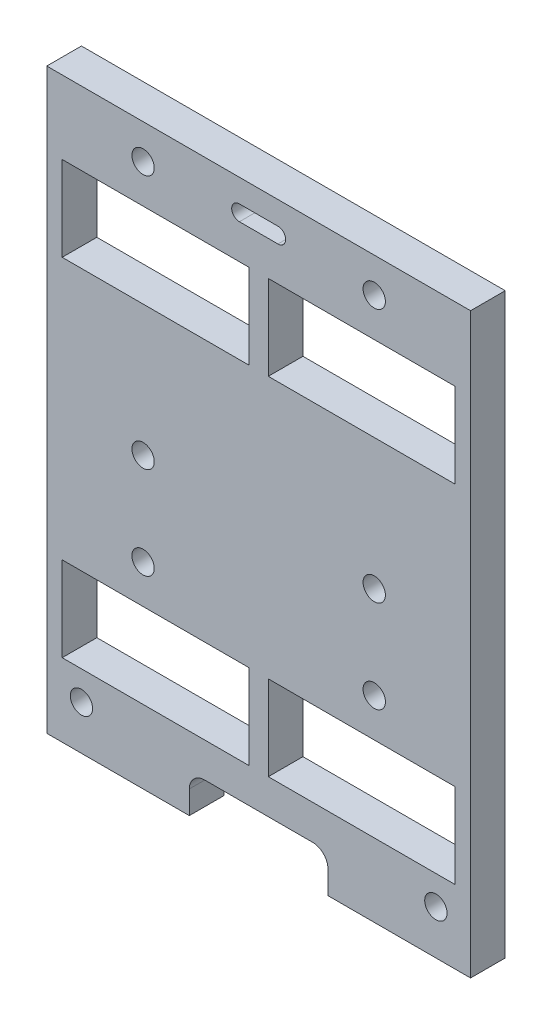
SolidWorks part; units mm, degrees
ref_plane "Front Plane" through (0, 0, 0) normal (0, 0, 1) x (1, 0, 0)
ref_plane "Top Plane" through (0, 0, 0) normal (0, 1, 0) x (1, 0, 0)
ref_plane "Right Plane" through (0, 0, 0) normal (1, 0, 0) x (0, 0, -1)
sketch "Sketch1" plane through (0, 0, 0) normal (0, 0, 1) x (1, 0, 0)
  line L0 (0, -37.5) -> (0, 37.5) construction
  line L1 (-27.5, -37.5) -> (27.5, -37.5)
  line L2 (-27.5, -37.5) -> (-27.5, 37.5)
  line L3 (-27.5, 37.5) -> (27.5, 37.5)
  line L4 (27.5, -37.5) -> (27.5, 37.5)
  line L5 (-27.5, -37.5) -> (27.5, 37.5) construction
  line L6 (-27.5, 37.5) -> (27.5, -37.5) construction
  line L7 (-27.5, 0) -> (27.5, 0) construction
  line L8 (-27.5, 22.5) -> (27.5, 22.5) construction
  line L9 (25.5, 17) -> (1.25, 28) construction
  line L10 (-25.5, 28) -> (-1.25, 28)
  line L11 (-25.5, 28) -> (-25.5, 17)
  line L12 (-25.5, 17) -> (-1.25, 17)
  line L13 (-1.25, 28) -> (-1.25, 17)
  line L14 (-25.5, 28) -> (-1.25, 17) construction
  line L15 (-25.5, 17) -> (-1.25, 28) construction
  line L16 (25.5, 28) -> (1.25, 17) construction
  line L17 (1.25, 28) -> (1.25, 17)
  line L18 (25.5, 17) -> (1.25, 17)
  line L19 (25.5, 28) -> (25.5, 17)
  line L20 (25.5, 28) -> (1.25, 28)
  line L21 (25.5, -28) -> (1.25, -17) construction
  line L22 (-25.5, -17) -> (-1.25, -28) construction
  line L23 (-25.5, -28) -> (-1.25, -17) construction
  line L24 (25.5, -17) -> (1.25, -28) construction
  line L25 (25.5, -28) -> (1.25, -28)
  line L26 (25.5, -28) -> (25.5, -17)
  line L27 (25.5, -17) -> (1.25, -17)
  line L28 (1.25, -28) -> (1.25, -17)
  line L29 (-1.25, -28) -> (-1.25, -17)
  line L30 (-25.5, -17) -> (-1.25, -17)
  line L31 (-25.5, -28) -> (-25.5, -17)
  line L32 (-25.5, -28) -> (-1.25, -28)
  point P0 (0, 0)
  point P12 (-13.375, 22.5)
  point P21 (13.375, 22.5)
  point P30 (13.375, -22.5)
  point P31 (-13.375, -22.5)
  dimension "D1" = 55
  dimension "D2" = 75
  dimension "D3" = 22.5
  dimension "D4" = 24.25
  dimension "D5" = 11
  dimension "D6" = 1.25
extrude "Boss-Extrude1" add sketch "Sketch1" along normal blind 4.5
sketch "Sketch2" plane through (0, 0, 4.5) normal (0, 0, 1) x (1, 0, 0)
  line L0 (0, -37.5) -> (0, 37.5) construction
  line L1 (-27.5, -37.5) -> (27.5, -37.5) construction
  line L2 (27.5, 37.5) -> (-27.5, 37.5) construction
  line L3 (-27.5, 0) -> (27.5, 0) construction
  line L4 (-27.5, 37.5) -> (-27.5, -37.5) construction
  line L5 (27.5, -37.5) -> (27.5, 37.5) construction
  line L6 (-15, 0) -> (15, 0) construction
  circle A0 centre (-15, 33) radius 1.45
  circle A1 centre (15, 33) radius 1.45
  circle A2 centre (15, 0) radius 1.45
  circle A3 centre (-15, 0) radius 1.45
  dimension "D1" = 2.9
  dimension "D7" = 2.9
  dimension "D8" = 2.9
  dimension "D2" = 15
  dimension "D3" = 33
  dimension "D4" = 30
  dimension "D5" = 15
  dimension "D6" = 0
extrude "screwHoles" cut sketch "Sketch2" against normal through all
sketch "Sketch3" plane through (0, 0, 4.5) normal (0, 0, 1) x (1, 0, 0)
  line L0 (-27.5, 9) -> (26.0486, 9) construction
  line L1 (-27.5, 37.5) -> (-27.5, -37.5) construction
  line L3 (0, 37.5) -> (0, -37.5) construction
  line L4 (27.5, 37.5) -> (-27.5, 37.5) construction
  line L5 (-27.5, -37.5) -> (27.5, -37.5) construction
  line L6 (18.95, 6.8) -> (9.05, 11.2) construction
  line L7 (-18.95, 11.2) -> (-9.05, 11.2)
  line L8 (-18.95, 11.2) -> (-18.95, 6.8)
  line L9 (-18.95, 6.8) -> (-9.05, 6.8)
  line L10 (-9.05, 11.2) -> (-9.05, 6.8)
  line L11 (-18.95, 11.2) -> (-9.05, 6.8) construction
  line L12 (-18.95, 6.8) -> (-9.05, 11.2) construction
  line L13 (18.95, 11.2) -> (9.05, 6.8) construction
  line L14 (9.05, 11.2) -> (9.05, 6.8)
  line L15 (18.95, 6.8) -> (9.05, 6.8)
  line L16 (18.95, 11.2) -> (18.95, 6.8)
  line L17 (18.95, 11.2) -> (9.05, 11.2)
  line L18 (-27.5, 37.5) -> (-27.5, -37.5) construction
  point P2 (-27.5, 0)
  point P12 (-14, 9)
  point P21 (14, 9)
  dimension "D1" = 9.9
  dimension "D2" = 4.4
  dimension "D3" = 14
  dimension "D4" = 9
extrude "BeltClamp" [suppressed] cut sketch "Sketch3" against normal through all
sketch "Sketch4" plane through (0, 0, 4.5) normal (0, 0, 1) x (1, 0, 0)
  line L0 (-27.5, 0) -> (27.5, 0) construction
  line L1 (-27.5, 37.5) -> (-27.5, -37.5) construction
  line L2 (27.5, -37.5) -> (27.5, 37.5) construction
  line L4 (-4.8, 2.15) -> (4.8, 2.15)
  line L5 (-4.8, 2.15) -> (-4.8, -2.15)
  line L6 (-4.8, -2.15) -> (4.8, -2.15)
  line L7 (4.8, 2.15) -> (4.8, -2.15)
  line L8 (-4.8, 2.15) -> (4.8, -2.15) construction
  line L9 (-4.8, -2.15) -> (4.8, 2.15) construction
  circle A0 centre (-15, 0) radius 1.45 construction
  point P6 (0, 0)
  dimension "D1" = 9.6
  dimension "D2" = 4.3
  dimension "D3" = 0
extrude "mountingPlateTab" [suppressed] cut sketch "Sketch4" against normal through all
sketch "Sketch5" plane through (0, 0, 4.5) normal (0, 0, 1) x (1, 0, 0)
  line L0 (-27.5, -9.75) -> (27.5, -9.75) construction
  line L1 (-27.5, 37.5) -> (-27.5, -37.5) construction
  line L2 (27.5, -37.5) -> (27.5, 37.5) construction
  line L4 (0, -37.5) -> (0, 37.5) construction
  line L5 (-27.5, -37.5) -> (27.5, -37.5) construction
  line L6 (27.5, 37.5) -> (-27.5, 37.5) construction
  line L7 (-20.85, -14.55) -> (-25.15, -4.95) construction
  line L8 (20.85, -4.95) -> (25.15, -4.95)
  line L9 (20.85, -4.95) -> (20.85, -14.55)
  line L10 (20.85, -14.55) -> (25.15, -14.55)
  line L11 (25.15, -4.95) -> (25.15, -14.55)
  line L12 (20.85, -4.95) -> (25.15, -14.55) construction
  line L13 (20.85, -14.55) -> (25.15, -4.95) construction
  line L14 (-20.85, -4.95) -> (-25.15, -14.55) construction
  line L15 (-25.15, -4.95) -> (-25.15, -14.55)
  line L16 (-20.85, -14.55) -> (-25.15, -14.55)
  line L17 (-20.85, -4.95) -> (-20.85, -14.55)
  line L18 (-20.85, -4.95) -> (-25.15, -4.95)
  line L19 (23, -9.75) -> (23, -37.5) construction
  line L20 (-23, -9.75) -> (-23, -37.5) construction
  circle A0 centre (23, -31.75) radius 1.45
  circle A1 centre (-23, -31.75) radius 1.45
  point P15 (23, -9.75)
  point P24 (-23, -9.75)
  dimension "D5" = 2.9
  dimension "D2" = 9.6
  dimension "D3" = 4.3
  dimension "D4" = 23
  dimension "D6" = 22
  dimension "D1" = 9.75
extrude "BraceTabs" cut sketch "Sketch5" against normal through all
sketch "Sketch6" [suppressed] plane through (0, 0, 4.5) normal (0, 0, 1) x (1, 0, 0)
  line L0 (-25.2, -9.75) -> (25.2, -9.75) construction
  line L1 (-25.2, -4.85) -> (-25.2, -14.65) construction
  line L2 (25.2, -14.65) -> (25.2, -4.85) construction
  line L3 (0, -2.2) -> (0, -37.5) construction
  line L4 (-4.9, -2.2) -> (4.9, -2.2) construction
  line L5 (-27.5, -37.5) -> (27.5, -37.5) construction
  line L6 (23, -14.65) -> (23, -4.85) construction
  line L7 (20.8, -14.65) -> (25.2, -14.65) construction
  line L8 (25.2, -4.85) -> (20.8, -4.85) construction
  line L9 (20.8, -4.85) -> (20.8, -14.65) construction
  line L10 (19.8, -15.65) -> (26.2, -15.65)
  line L11 (19.8, -15.65) -> (19.8, -3.85)
  line L12 (19.8, -3.85) -> (26.2, -3.85)
  line L13 (26.2, -15.65) -> (26.2, -3.85)
  line L14 (19.8, -15.65) -> (26.2, -3.85) construction
  line L15 (19.8, -3.85) -> (26.2, -15.65) construction
  line L16 (-19.8, -3.85) -> (-26.2, -15.65) construction
  line L17 (-19.8, -15.65) -> (-26.2, -3.85) construction
  line L18 (-23, -14.65) -> (-23, -4.85) construction
  line L19 (-26.2, -15.65) -> (-26.2, -3.85)
  line L20 (-19.8, -3.85) -> (-26.2, -3.85)
  line L21 (-19.8, -15.65) -> (-19.8, -3.85)
  line L22 (-19.8, -15.65) -> (-26.2, -15.65)
  circle A0 centre (23, -9.75) radius 1.45
  circle A1 centre (-23, -9.75) radius 1.45
  point P18 (23, -9.75)
  dimension "D3" = 2.9
  dimension "D1" = 1
  dimension "D2" = 1
extrude "FrontToRear1" [suppressed] add sketch "Sketch6" against normal up to surface (4.5 mm away) up to face at (-24.45, -31.75, 0)
sketch "Sketch7" [suppressed] plane through (0, 0, 4.5) normal (0, 0, 1) x (1, 0, 0)
  line L0 (4.9, 2.2) -> (-4.9, 2.2) construction
  line L1 (-20, -3.2) -> (20, -3.2)
  line L2 (-20, -3.2) -> (-20, 3.2)
  line L3 (-20, 3.2) -> (20, 3.2)
  line L4 (20, -3.2) -> (20, 3.2)
  line L5 (-20, -3.2) -> (20, 3.2) construction
  line L6 (-20, 3.2) -> (20, -3.2) construction
  circle A0 centre (15, 0) radius 1.45 construction
  point P0 (0, 0)
  dimension "D1" = 1
  dimension "D2" = 5
extrude "FrontToRear2" [suppressed] add sketch "Sketch7" against normal through all
sketch "Sketch8" plane through (0, 0, 4.5) normal (0, 0, 1) x (1, 0, 0)
  line L0 (-27.5, -12) -> (27.5, -12) construction
  line L1 (-27.5, 37.5) -> (-27.5, -37.5) construction
  line L2 (27.5, -37.5) -> (27.5, 37.5) construction
  line L3 (0, -37.5) -> (0, 0) construction
  line L4 (-27.5, -37.5) -> (27.5, -37.5) construction
  circle A0 centre (-15, -12) radius 1.45
  circle A1 centre (15, -12) radius 1.45
  dimension "D2" = 2.9
  dimension "D1" = 12
  dimension "D3" = 15
extrude "ExpansionScrewholes" cut sketch "Sketch8" against normal through all
sketch "Sketch12" plane through (0, 0, 4.5) normal (0, 0, 1) x (1, 0, 0)
  line L0 (0, 37.5) -> (0, 0) construction
  line L1 (27.5, 37.5) -> (-27.5, 37.5) construction
  line L2 (-2.5, 33.5) -> (2.5, 33.5) construction
  line L3 (-2.5, 34.5) -> (2.5, 34.5)
  line L4 (-2.5, 32.5) -> (2.5, 32.5)
  arc A0 (-2.5, 34.5) -> (-2.5, 32.5) centre (-2.5, 33.5) ccw
  arc A1 (2.5, 32.5) -> (2.5, 34.5) centre (2.5, 33.5) ccw
  point P7 (0, 33.5)
  dimension "D1" = 3
  dimension "D2" = 2
  dimension "D3" = 5
extrude "CableTieSlot" cut sketch "Sketch12" against normal through all
sketch "Sketch11" plane through (0, 0, 4.5) normal (0, 0, 1) x (1, 0, 0)
  line L0 (13.5615, -8.55) -> (27.5, -8.55) construction
  line L1 (27.5, -37.5) -> (27.5, 37.5) construction
  line L2 (0, 37.5) -> (0, -37.5) construction
  line L3 (36.5, -14.55) -> (18.5, -14.55)
  line L4 (36.5, -14.55) -> (36.5, -2.55)
  line L5 (36.5, -2.55) -> (18.5, -2.55)
  line L6 (18.5, -14.55) -> (18.5, -2.55)
  line L7 (36.5, -14.55) -> (18.5, -2.55) construction
  line L8 (36.5, -2.55) -> (18.5, -14.55) construction
  line L11 (-36.5, -2.55) -> (-18.5, -14.55) construction
  line L12 (-36.5, -14.55) -> (-18.5, -2.55) construction
  line L13 (-18.5, -14.55) -> (-18.5, -2.55)
  line L14 (-36.5, -2.55) -> (-18.5, -2.55)
  line L15 (-36.5, -14.55) -> (-36.5, -2.55)
  line L16 (-36.5, -14.55) -> (-18.5, -14.55)
  line L17 (36.5, -2.55) -> (18.5, -14.55) construction
  line L18 (20.85, -14.55) -> (25.15, -14.55) construction
  line L19 (27.5, 37.5) -> (-27.5, 37.5) construction
  line L20 (-27.5, -37.5) -> (27.5, -37.5) construction
  dimension "D1" = 9
  dimension "D2" = 12
  dimension "D3" = 0
extrude "Cut-Extrude2" [suppressed] cut sketch "Sketch11" against normal through all
sketch "Sketch10" [suppressed] plane through (0, 0, 4.5) normal (0, 0, 1) x (1, 0, 0)
  line L0 (4.7446, 1) -> (27.5, 1) construction
  line L1 (-4.9, 0) -> (4.9, 0) construction
  line L2 (27.5, -37.5) -> (27.5, 37.5) construction
  line L3 (0, 2.2) -> (0, -2.2) construction
  line L4 (36.5, 4) -> (18.5, 4)
  line L5 (36.5, 4) -> (36.5, -2)
  line L6 (36.5, -2) -> (18.5, -2)
  line L7 (18.5, 4) -> (18.5, -2)
  line L8 (36.5, 4) -> (18.5, -2) construction
  line L9 (36.5, -2) -> (18.5, 4) construction
  line L10 (4.9, 2.2) -> (-4.9, 2.2) construction
  line L11 (-4.9, -2.2) -> (4.9, -2.2) construction
  line L12 (-36.5, -2) -> (-18.5, 4) construction
  line L13 (-36.5, 4) -> (-18.5, -2) construction
  line L14 (-4.7446, 1) -> (-27.5, 1) construction
  line L15 (-18.5, 4) -> (-18.5, -2)
  line L16 (-36.5, -2) -> (-18.5, -2)
  line L17 (-36.5, 4) -> (-36.5, -2)
  line L18 (-36.5, 4) -> (-18.5, 4)
  line L19 (36.5, -2) -> (18.5, 4) construction
  line L20 (-4.9, 2.2) -> (-4.9, -2.2) construction
  line L21 (4.9, -2.2) -> (4.9, 2.2) construction
  dimension "D1" = 6
  dimension "D2" = 9
  dimension "D3" = 1
extrude "CableTieSlots" [suppressed] cut sketch "Sketch10" against normal through all
sketch "Sketch9" plane through (0, 0, 4.5) normal (0, 0, 1) x (1, 0, 0)
  line L0 (-27.5, -37.5) -> (27.5, -37.5) construction
  line L5 (-9, -42.5) -> (9, -42.5)
  line L6 (-9, -42.5) -> (-9, -34.5)
  line L7 (-7, -32.5) -> (7, -32.5)
  line L8 (9, -42.5) -> (9, -34.5)
  line L9 (-9, -42.5) -> (9, -32.5) construction
  line L10 (-9, -32.5) -> (9, -42.5) construction
  arc A0 (7, -32.5) -> (9, -34.5) centre (7, -34.5) cw
  arc A1 (-9, -34.5) -> (-7, -32.5) centre (-7, -34.5) cw
  point P9 (0, -37.5)
  line M42 (-27.5, -37.5) -> (27.5, -37.5)
  dimension "D3" = 2
  dimension "D1" = 18
  dimension "D2" = 5
extrude "RearFanSlot" cut sketch "Sketch9" against normal through all contours A1 L6 L8 A0 L7 M42 | L5 L8 L6 M42
sketch "Sketch13" [suppressed] plane through (0, 0, 4.5) normal (0, 0, 1) x (1, 0, 0)
  line L1 (-7, -2.85) -> (7, -2.85)
  line L2 (-7, -2.85) -> (-7, -11.85)
  line L3 (-7, -11.85) -> (7, -11.85)
  line L4 (7, -2.85) -> (7, -11.85)
  line L5 (-7, -2.85) -> (7, -11.85) construction
  line L6 (-7, -11.85) -> (7, -2.85) construction
  line L9 (0, 37.5) -> (0, -7.35) construction
  line L10 (-18.5, -2.85) -> (-27.5, -2.85) construction
  line L11 (27.5, 37.5) -> (-27.5, 37.5) construction
  line L13 (-27.5, -14.85) -> (-18.5, -14.85) construction
  point P0 (0, -7.35)
  dimension "D1" = 3
  dimension "D2" = 0
  dimension "D3" = 7
extrude "Cut-Extrude3" [suppressed] cut sketch "Sketch13" against normal through all
sketch "Sketch14" plane through (0, 0, 4.5) normal (0, 0, 1) x (1, 0, 0)
  line L0 (25.15, -4.95) -> (20.85, -4.95) construction
  line L1 (25.15, -4.95) -> (20.85, -4.95)
  line L2 (25.15, -4.95) -> (25.15, -14.55)
  line L3 (25.15, -14.55) -> (20.85, -14.55)
  line L4 (20.85, -4.95) -> (20.85, -14.55)
  line L5 (25.15, -14.55) -> (25.15, -4.95) construction
  line L6 (0, 0) -> (0, -6.835) construction
  line L7 (-20.85, -4.95) -> (-20.85, -14.55)
  line L8 (-25.15, -14.55) -> (-20.85, -14.55)
  line L9 (-25.15, -4.95) -> (-25.15, -14.55)
  line L10 (-25.15, -4.95) -> (-20.85, -4.95)
extrude "Boss-Extrude2" add sketch "Sketch14" against normal through all
equation "\"X-ROD-SPACING\"=45"
equation "\"Y-ROD-SPACING\"=75"
equation "\"Z-ROD-SPACING\"=17.5"
equation "\"Y-BED-OFFSET\"=2"
equation "\"Y-BED-ROD-INSET\"=3.5"
equation "\"Y-BED-SCREW-SPACING\"=209"
equation "\"Y-BED-SCREW-CUTOUT-SLOT-HEIGHT\"=2"
equation "\"T-SLOT-NUT-FILLET-RADIUS\"=0.5"
equation "\"T-SLOT-SCREW-SHAFT-RADIUS\"=1.55"
equation "\"T-SLOT-SCREW-SHAFT-CUTOUT-LENGTH\"=11.0"
equation "\"T-SLOT-NUT-DEPTH\"=3.5"
equation "\"T-SLOT-NUT-WIDTH\"=2.85"
equation "\"T-SLOT-NUT-END-DISTANCE\"=8"
equation "\"ACRYLIC-THICKNESS\"=10"
equation "\"ACRYLIC-THICKNESS2\"=4.5"
equation "\"ACRYLIC-TAB-CUTOUT-SIZE\"=\"ACRYLIC-THICKNESS\"+\"ACRYLIC-TAB-TOLERANCE\"*2"
equation "\"ACRYLIC-TAB-WIDTH\"=\"ACRYLIC-THICKNESS\""
equation "\"ACRYLIC-M3-HOLE\"=2.9"
equation "\"SMOOTHROD-CAP-SCREW-DISTANCE\"=20"
equation "\"FRAME-WIDTH-INNER\"=370"
equation "\"NEMA17-HOLE-SPACING\"=31"
equation "\"NEMA17-CENTRAL-CUTOUT\"=22.5"
equation "\"Z-BRACKET-REACH\"=55"
equation "\"Z-ROD-INSET\"=16"
equation "\"TOP-BRACKET-SPACING\"=40"
equation "\"SMOOTHROD-X-LENGTH\"=350"
equation "\"SMOOTHROD-Y-LENGTH\"=350"
equation "\"SMOOTHROD-Z-LENGTH\"=350"
equation "\"SMOOTHROD-TIGHTENING-HEADROOM\"=.25"
equation "\"LEADSCREW-Z-LENGTH\"=300"
equation "\"SCREW-LENGTH-FRAME\"=\"ACRYLIC-THICKNESS\" + 10"
equation "\"SCREW-LENGTH-MOTOR\"=\"ACRYLIC-THICKNESS\" + 5"
equation "\"SCREW-HEAD-RADIUS\"=6"
equation "\"PRINTED-X-SMOOTHROD-DIAMETER\"=9.0"
equation "\"PRINTED-X-SMOOTHROD-CUTOUT\"=10"
equation "\"PRINTED-X-BASE-HEIGHT\"=10"
equation "\"PRINTED-LM8UU-CUTOUT-SIZE\"=15.5"
equation "\"PRINTED-LM8UU-CUTOUT-LENGTH\"=24.5"
equation "\"PRINTED-X-IDLER-HEIGHT\"=16"
equation "\"PSU-MOUNTING-WIDTH\"=95"
equation "\"PSU-MOUNTING-HEIGHT\"=177"
equation "\"Y-BELT-TO-ROD-DISTANCE\"=20"
equation "\"SPOOL-HOLDER-ROD-SPACING\"=150"
equation "\"D3@Sketch1\"=\"X-ROD-SPACING\"/2"
equation "\"D4@Sketch1\"=\"ACRYLIC-X-CARRIAGE-LM8UU-CUTOUT-WIDTH\""
equation "\"D1@Boss-Extrude1\"=\"ACRYLIC-THICKNESS2\""
equation "\"D1@Sketch2\"=\"ACRYLIC-M3-HOLE\""
equation "\"D1@Sketch3\"=\"ACRYLIC-TAB-CUTOUT-SIZE\""
equation "\"D2@Sketch3\"=\"ACRYLIC-THICKNESS2\"+\"ACRYLIC-TAB-TOLERANCE\"*2"
equation "\"ACRYLIC-X-CARRIAGE-WIDTH\"=55"
equation "\"ACRYLIC-X-CARRIAGE-HEIGHT\"=75"
equation "\"D1@Sketch1\"=\"ACRYLIC-X-CARRIAGE-WIDTH\""
equation "\"D2@Sketch1\"=\"ACRYLIC-X-CARRIAGE-HEIGHT\""
equation "\"ACRYLIC-X-CARRIAGE-CENTER-TAB-SPACING\"=14"
equation "\"D3@Sketch3\"=\"ACRYLIC-X-CARRIAGE-CENTER-TAB-SPACING\""
equation "\"SCREW-LENGTH-EXTRUDER\"=28"
equation "\"ACRYLIC-X-CARRIAGE-SCREW-SPACING-X\"=15"
equation "\"ACRYLIC-X-CARRIAGE-SCREW-SPACING-Y\"=33"
equation "\"D2@Sketch2\"=\"ACRYLIC-X-CARRIAGE-SCREW-SPACING-X\""
equation "\"D3@Sketch2\"=\"ACRYLIC-X-CARRIAGE-SCREW-SPACING-Y\""
equation "\"D1@Sketch4\"=\"ACRYLIC-TAB-WIDTH\"-\"KERF\"*4"
equation "\"D2@Sketch4\"=\"ACRYLIC-THICKNESS2\"-\"KERF\"*2"
equation "\"D2@Sketch5\"=\"ACRYLIC-TAB-WIDTH\"-\"KERF\"*4"
equation "\"D3@Sketch5\"=\"ACRYLIC-THICKNESS2\"-\"KERF\"*2"
equation "\"ACRYLIC-X-CARRIAGE-EXTRUDER-SHELF-DEPTH\"=\"ACRYLIC-X-CARRIAGE-EXTRUDER-OFFSET\" + 28"
equation "\"ACRYLIC-X-CARRIAGE-EXTRUDER-BRACE-SPACING\"=23"
equation "\"D4@Sketch5\"=\"ACRYLIC-X-CARRIAGE-EXTRUDER-BRACE-SPACING\""
equation "\"D4@Sketch2\"=\"ACRYLIC-X-CARRIAGE-SCREW-SPACING-X\"*2"
equation "\"D5@Sketch2\"=\"ACRYLIC-X-CARRIAGE-SCREW-SPACING-X\""
equation "\"D7@Sketch2\"=\"ACRYLIC-M3-HOLE\""
equation "\"D8@Sketch2\"=\"ACRYLIC-M3-HOLE\""
equation "\"ACRYLIC-X-CARRIAGE-LM8UU-CUTOUT-WIDTH\"=24.25"
equation "\"ACRYLIC-TAB-TOLERANCE\"=-.05"
equation "\"ACRYLIC-X-CARRIAGE-EXTRUDER-OFFSET\"=26"
equation "\"ACRYLIC-X-CARRIAGE-EXTRUDER-ANGLE\"=90"
equation "\"ACRYLIC-X-CARRIAGE-EXTRUDER-BRACE-TAB-OFFSET\"=20"
equation "\"ACRYLIC-X-CARRIAGE-EXTRUDER-BRACE-HEIGHT\"=35"
equation "\"ACRYLIC-X-CARRIAGE-EXTRUDER-BRACE-SCREW-SPACING\"=22"
equation "\"D5@Sketch5\"=\"ACRYLIC-M3-HOLE\""
equation "\"D3@Sketch6\"=\"ACRYLIC-M3-HOLE\""
equation "\"ACRYLIC-X-CARRIAGE-LM8UU-CUTOUT-HEIGHT\"=11.0"
equation "\"ACRYLIC-X-CARRIAGE-DUAL-WIDTH-MULTIPLIER\"=1.65"
equation "\"ACRYLIC-X-CARRIAGE-DUAL-HOTEND-SPACING\"=42"
equation "\"ACRYLIC-X-CARRIAGE-DUAL-WIDTH\"=75"
equation "\"ACRYLIC-X-CARRIAGE-DUAL-HOTEND-SEPARATION\"=36"
equation "\"ACRYLIC-X-CARRIAGE-DUAL-MOUNT-PLATE-DEPTH\"=75"
equation "\"ACRYLIC-X-CARRIAGE-DUAL-MOUNT-BRACE-WIDTH\"=33"
equation "\"ACRYLIC-X-CARRIAGE-DUAL-MOUNT-SCREW-WIDTH\"=40"
equation "\"D5@Sketch1\"=\"ACRYLIC-X-CARRIAGE-LM8UU-CUTOUT-HEIGHT\""
equation "\"D2@Sketch8\"=\"ACRYLIC-M3-HOLE\""
equation "\"D1@Sketch5\"=\"ACRYLIC-THICKNESS2\"/2 + 7.5"
equation "\"KERF\"=0.1"
equation "\"PRINTED-M3-HOLE\"=3.5"
equation "\"PRINTED-M3-NUT-AF\"=6.25"
equation "\"ACRYLIC-X-CARRIAGE-DUAL-FAN-OFFSET\"=52"
equation "\"ACRYLIC-X-CARRIAGE-DUAL-FAN-HEIGHT\"=20"
equation "\"BLOWER-FAN-WIDTH\"=15"
